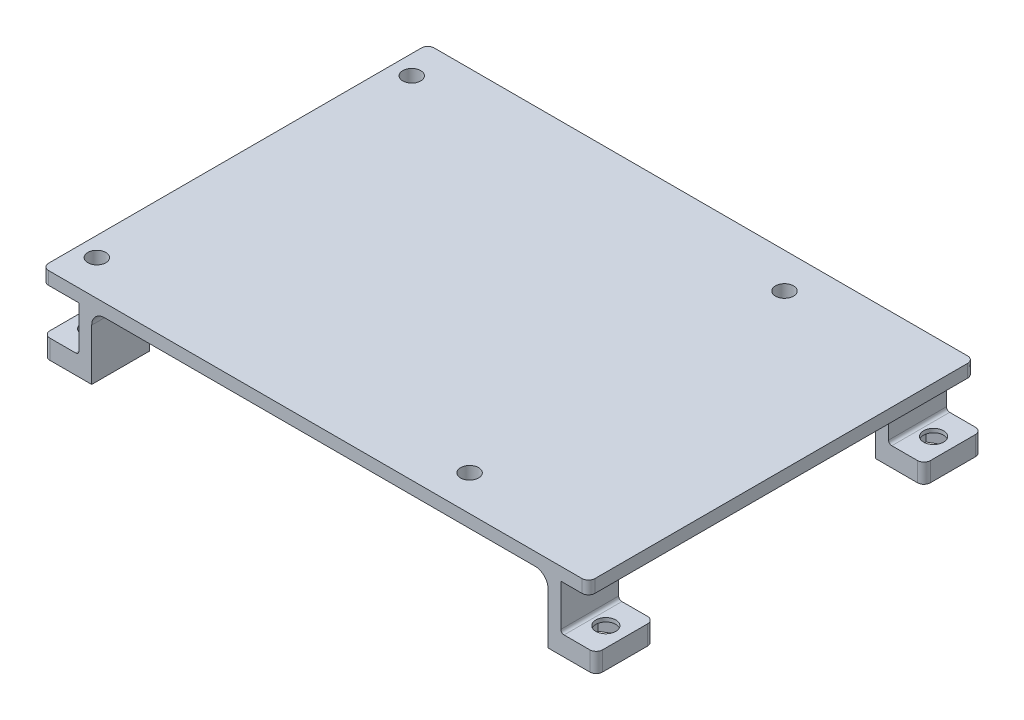
SolidWorks part; units mm, degrees
ref_plane "前基準面" through (0, 0, 0) normal (0, 0, 1) x (1, 0, 0)
ref_plane "上基準面" through (0, 0, 0) normal (0, 1, 0) x (1, 0, 0)
ref_plane "右基準面" through (0, 0, 0) normal (1, 0, 0) x (0, 0, -1)
sketch "草圖1" plane through (0, 0, 0) normal (0, 0, 1) x (1, 0, 0)
  line L0 (-133.4262, 0) -> (6537.8852, 0) construction
  line L1 (0, -133.4262) -> (0, 6537.8852) construction
  line L2 (-43, 0) -> (-43, 3)
  line L3 (-43, 3) -> (-37.5, 3)
  line L4 (-37.5, 3) -> (-37.5, 10)
  line L6 (37.5, 10) -> (37.5, 3)
  line L7 (37.5, 3) -> (43, 3)
  line L8 (43, 3) -> (43, 0)
  line L10 (-35.5, 0) -> (-35.5, 10)
  line L11 (-35.5, 10) -> (35.5, 10)
  line L12 (35.5, 10) -> (35.5, 0)
  line L13 (-43, 0) -> (-35.5, 0)
  line L14 (35.5, 0) -> (43, 0)
  line L16 (-43.2, 12) -> (-43.2, 10)
  line L17 (-37.5, 10) -> (-43.2, 10)
  line L18 (-43.2, 12) -> (41.8, 12)
  line L19 (41.8, 12) -> (41.8, 10)
  line L20 (41.8, 10) -> (37.5, 10)
  dimension "D1" = 2
  dimension "D2" = 10
  dimension "D3" = 71
  dimension "D4" = 86
  dimension "D5" = 2
  dimension "D6" = 3
  dimension "D7" = 85
  dimension "D8" = 5.7
extrude "填料-伸長1" add sketch "草圖1" along normal mid plane 60
sketch "草圖8" plane through (0, 0, 0) normal (0, 0, 1) x (1, 0, 0)
  line L0 (41.8, 12) -> (-43.2, 12) construction
  line L2 (35.5, 10) -> (35.5, 0) construction
  line L4 (-35.5, 10) -> (35.5, 10) construction
  line L5 (-35.5, 0) -> (-35.5, 10) construction
  line L6 (37.5, 12) -> (-37.5072, 12)
  line L7 (35.5, 0) -> (43, 0) construction
  line L8 (35.5, 10) -> (35.5, 0)
  line L9 (-35.5, 0) -> (-37.5072, 0)
  line L10 (-35.5, 10) -> (35.5, 10)
  line L11 (-35.5, 0) -> (-35.5, 10)
  line L12 (37.5, 0) -> (37.5, 12)
  line L13 (35.5, 0) -> (37.5, 0)
  line L14 (-37.5072, 12) -> (-37.5072, 0)
sketch "草圖2" plane through (0, 0, 0) normal (1, 0, 0) x (0, 0, -1)
  line L0 (-1000, 0) -> (49000, 0) construction
  line L1 (0, -1000) -> (0, 49000) construction
  line L3 (-21, -6) -> (21, -6)
  line L4 (-21, -6) -> (-21, 6)
  line L5 (-21, 6) -> (21, 6)
  line L6 (21, -6) -> (21, 6)
  line L7 (-21, -6) -> (21, 6) construction
  line L8 (-21, 6) -> (21, -6) construction
  point P4 (0, 0)
  dimension "D1" = 42
  dimension "D2" = 12
extrude "除料-伸長1" cut sketch "草圖2" against normal through all both and the other way through all
sketch "草圖3" plane through (0, 0, 0) normal (0, 1, 0) x (1, 0, 0)
  line L0 (-40, -1017.5) -> (-40, 48982.5) construction
  line L2 (40, -1017.5) -> (40, 48982.5) construction
  line L4 (-1031.5, 25.5) -> (48968.5, 25.5) construction
  line L5 (0, -1000) -> (0, 49000) construction
  line L6 (-1031.5, -25.5) -> (48968.5, -25.5) construction
  line L8 (-1000, 0) -> (49000, 0) construction
  line L9 (-43.2, -30) -> (-37.5, -30) construction
  line L10 (35.5, -30) -> (43, -30) construction
  circle A0 centre (-40, 25.5) radius 1.55
  circle A1 centre (40, 25.5) radius 1.55
  circle A2 centre (40, -25.5) radius 1.55
  circle A3 centre (-40, -25.5) radius 1.55
  point P12 (-40, -30)
  point P16 (40, -30)
  dimension "D1" = 3.1
  dimension "D2" = 51
  dimension "D3" = 80
extrude "除料-伸長4" cut sketch "草圖3" along normal up to next contours A0 | A1 | A3 | A2
sketch "草圖5" plane through (0, 12, 0) normal (0, 1, 0) x (1, 0, 0)
  line L0 (-1000, 0) -> (49000, 0) construction
  line L1 (-1033.1907, 24.5) -> (48966.8093, 24.5) construction
  line L2 (-1033.1907, -24.5) -> (48966.8093, -24.5) construction
  line L3 (-40.2, 24.5) -> (-40.2, -24.5) construction
  line L4 (17.8, 24.5) -> (17.8, -24.5) construction
  line L5 (-43.2, -30) -> (-43.2, 30) construction
  circle A0 centre (-40.2, 24.5) radius 1.4
  circle A1 centre (-40.2, -24.5) radius 1.4
  circle A2 centre (17.8, 24.5) radius 1.4
  circle A3 centre (17.8, -24.5) radius 1.4
  dimension "D3" = 2.8
  dimension "D1" = 49
  dimension "D2" = 24.5
  dimension "D4" = 58
  dimension "D5" = 3
extrude "除料-伸長5" cut sketch "草圖5" against normal blind 5
ref_plane "平面1" through (0, 3, 0) normal (0, 1, 0) x (1, 0, 0)
sketch "草圖16" plane through (0, 0, 0) normal (0, -1, 0) x (1, 0, 0)
  line L0 (-59.8233, 0) -> (72.7296, 0) construction
  line L1 (-40, 22.2091) -> (-37.15, 23.8546)
  line L2 (-37.15, 23.8546) -> (-37.15, 27.1454)
  line L3 (-37.15, 27.1454) -> (-40, 28.7909)
  line L4 (-40, 28.7909) -> (-42.85, 27.1454)
  line L5 (-42.85, 27.1454) -> (-42.85, 23.8546)
  line L6 (-42.85, 23.8546) -> (-40, 22.2091)
  line L7 (-42.85, -23.8546) -> (-40, -22.2091)
  line L8 (0, 58.8179) -> (0, -48.0944) construction
  line L9 (-42.85, -27.1454) -> (-42.85, -23.8546)
  line L10 (-40, -28.7909) -> (-42.85, -27.1454)
  line L11 (-37.15, -27.1454) -> (-40, -28.7909)
  line L12 (-37.15, -23.8546) -> (-37.15, -27.1454)
  line L13 (-40, -22.2091) -> (-37.15, -23.8546)
  line L14 (40, -22.2091) -> (37.15, -23.8546)
  line L15 (37.15, -23.8546) -> (37.15, -27.1454)
  line L16 (37.15, -27.1454) -> (40, -28.7909)
  line L17 (40, -28.7909) -> (42.85, -27.1454)
  line L18 (42.85, -27.1454) -> (42.85, -23.8546)
  line L19 (42.85, -23.8546) -> (40, -22.2091)
  line L20 (42.85, 23.8546) -> (40, 22.2091)
  line L21 (42.85, 27.1454) -> (42.85, 23.8546)
  line L22 (40, 28.7909) -> (42.85, 27.1454)
  line L23 (37.15, 27.1454) -> (40, 28.7909)
  line L24 (37.15, 23.8546) -> (37.15, 27.1454)
  line L25 (40, 22.2091) -> (37.15, 23.8546)
  circle A0 centre (-40, 25.5) radius 2.85 construction
  circle A1 centre (-40, -25.5) radius 2.85 construction
  circle A2 centre (40, -25.5) radius 2.85 construction
  circle A3 centre (40, 25.5) radius 2.85 construction
  dimension "D1" = 5.7
extrude "除料-伸長7" cut sketch "草圖16" against normal blind 2.4
fillet "圓角1" radius 1 12 edges at (41.8, 11, -30) (43, 1.5, -30) (43, 1.5, -21) (43, 1.5, 21) (43, 1.5, 30) (41.8, 11, 30) (-43.2, 11, -30) (-43, 1.5, -30) (-43, 1.5, -21) (-43, 1.5, 21) (-43, 1.5, 30) (-43.2, 11, 30)
fillet "圓角5" radius 0.5 4 edges at (37.5, 3, -25.5) (37.5, 3, 25.5) (-37.5, 3, -25.5) (-37.5, 3, 25.5)
fillet "圓角7" radius 2 2 edges at (35.5, 10, 0) (-35.5, 10, 0)
